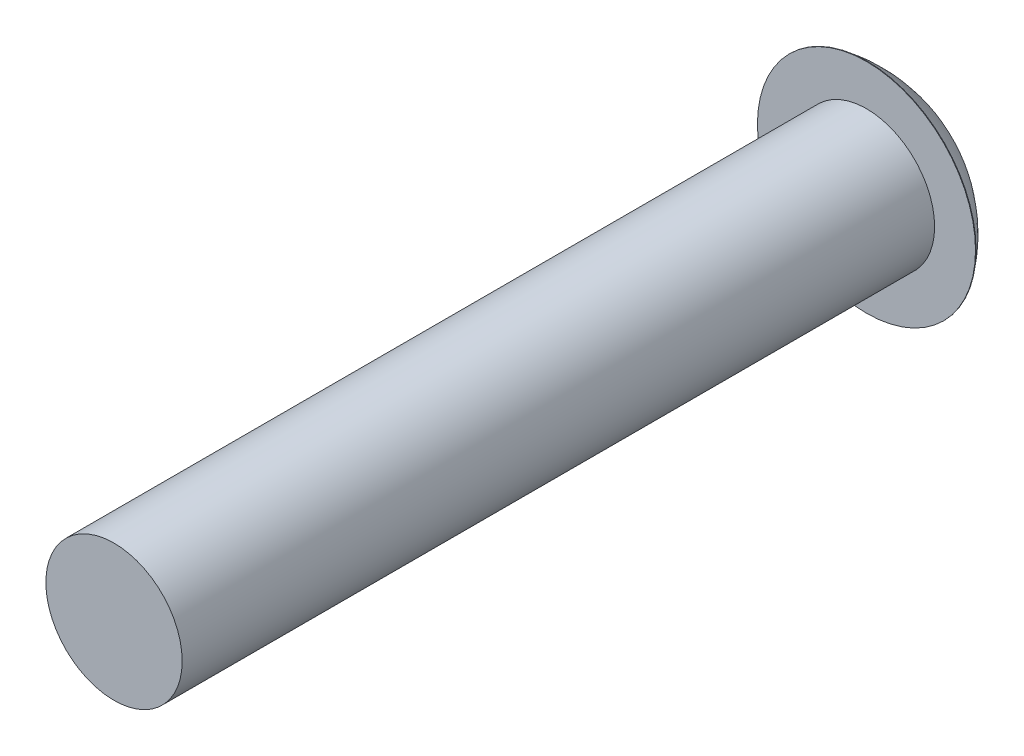
SolidWorks part; units mm, degrees
ref_plane "Front Plane" through (0, 0, 0) normal (0, 0, 1) x (1, 0, 0)
ref_plane "Top Plane" through (0, 0, 0) normal (0, 1, 0) x (1, 0, 0)
ref_plane "Right Plane" through (0, 0, 0) normal (1, 0, 0) x (0, 0, -1)
sketch "Sketch1" plane through (0, 0, 0) normal (0, 0, 1) x (1, 0, 0)
  circle A0 centre (0, 0) radius 1.25
  dimension "D1" = 2.5
extrude "Boss-Extrude1" add sketch "Sketch1" along normal blind 13.8
cosmetic thread "Cosmetic Thread1" parameters "D1"=5.0365, "D2"=1.993
sketch "Sketch3" plane through (0, 0, 0) normal (0, 0, -1) x (-1, 0, 0)
  circle A1 centre (0, 0) radius 2
extrude "Boss-Extrude2" add sketch "Sketch3" along normal blind 0.01
dome "Dome1" faces to dome 1 distance 1 reverse direction no elliptical dome no face at (-2, 0, -0.01) parameters "D1"=1
scale "Scale1" scale about centroid uniform scaling yes scale factor 1.5
